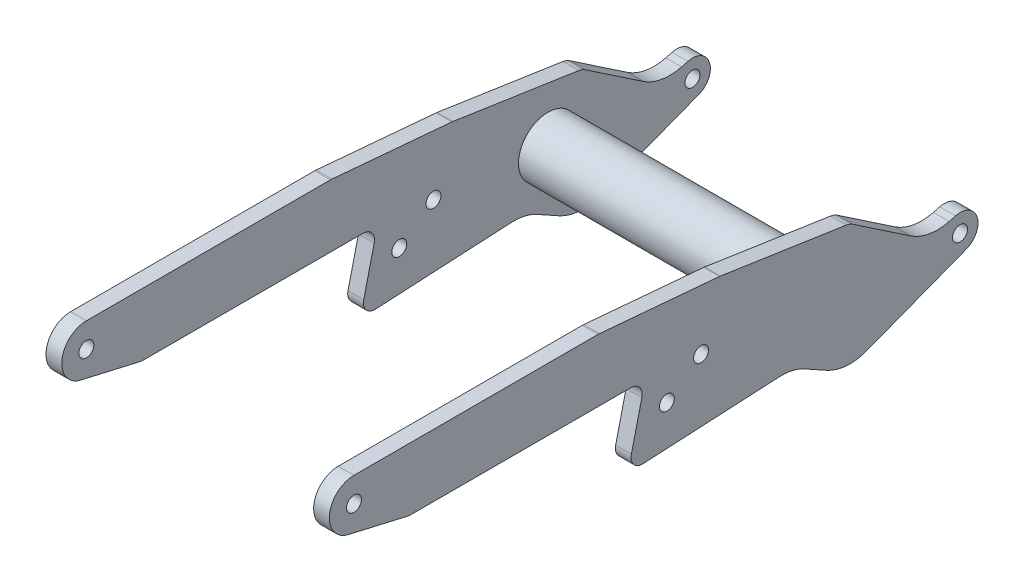
SolidWorks part; units mm, degrees
ref_plane "Front Plane" through (0, 0, 0) normal (0, 0, 1) x (1, 0, 0)
ref_plane "Top Plane" through (0, 0, 0) normal (0, 1, 0) x (1, 0, 0)
ref_plane "Right Plane" through (0, 0, 0) normal (1, 0, 0) x (0, 0, -1)
sketch "Sketch1" plane through (0, 0, 0) normal (1, 0, 0) x (0, 0, -1)
  line L0 (0, 15.625) -> (155.5, 15.625)
  line L1 (0, 0) -> (0, 24.103) construction
  line L2 (0, 0) -> (385.2736, 0) construction
  line L3 (155.5, 15.625) -> (232.5, 8.8884)
  line L4 (232.5, 8.8884) -> (315, -3.4413)
  line L5 (315, -3.4413) -> (353.7804, -29.5991)
  line L6 (378.0985, -33.7644) -> (382.1339, -32.7162)
  line L7 (-3.5149, -15.2245) -> (35, -24.1164)
  line L8 (35, -24.1164) -> (175.8144, -24.1164)
  line L9 (182.866, -33.0507) -> (176.2129, -60.9055)
  line L10 (183.6448, -69.8298) -> (270.1595, -65.2859)
  line L11 (286.2743, -69.0044) -> (300.5448, -76.9126)
  line L12 (325.8403, -78.6785) -> (389.0866, -54.3924)
  circle A0 centre (0, 0) radius 4.75
  circle A1 centre (198.75, -43.75) radius 4.75
  circle A2 centre (220.5, -28) radius 4.75
  circle A3 centre (385, -43.75) radius 4.75
  arc A4 (0, 15.625) -> (-3.5149, -15.2245) centre (0, 0) ccw
  arc A5 (382.1339, -32.7162) -> (389.0866, -54.3924) centre (385, -43.75) cw
  arc A6 (353.7804, -29.5991) -> (378.0985, -33.7644) centre (370.5562, -4.7279) ccw
  arc A7 (325.8403, -78.6785) -> (300.5448, -76.9126) centre (315.0861, -50.6723) cw
  arc A8 (286.2743, -69.0044) -> (270.1595, -65.2859) centre (271.7329, -95.2446) ccw
  arc A9 (183.6448, -69.8298) -> (176.2129, -60.9055) centre (183.2645, -62.5898) cw
  arc A10 (182.866, -33.0507) -> (175.8144, -24.1164) centre (175.8144, -31.3664) ccw
  point P26 (365, -37.1668)
  point P31 (278.75, -64.8347)
  point P36 (185, -24.1164)
  dimension "D1" = 9.5
  dimension "D8" = 15.625
  dimension "D9" = 154.5
  dimension "D15" = 11.4
  dimension "D17" = 35
  dimension "D24" = 30
  dimension "D25" = 7.25
  dimension "D2" = 198.75
  dimension "D3" = 43.75
  dimension "D4" = 220.5
  dimension "D5" = 28
  dimension "D6" = 385
  dimension "D7" = 43.75
  dimension "D10" = 155.5
  dimension "D11" = 232.5
  dimension "D12" = 315
  dimension "D13" = 175
  dimension "D14" = 176.5
  dimension "D16" = 50
  dimension "D18" = 167
  dimension "D19" = 150
  dimension "D20" = 73.56
  dimension "D21" = 148
  dimension "D22" = 130
  dimension "D23" = 80
extrude "Boss-Extrude1" add sketch "Sketch1" along normal mid plane 180
fillet "Fillet1" radius 10 4 edges at (0, -24.1164, -35) (0, -3.4413, -315) (0, 8.8884, -232.5) (0, 15.625, -155.5)
ref_plane "Plane2" through (0, 15.625, 0) normal (0, 1, 0) x (1, 0, 0)
sketch "Sketch4" plane through (0, 15.625, 0) normal (0, 1, 0) x (1, 0, 0)
  line L0 (-90, -15.625) -> (90, -15.625) construction
  line L1 (-80, -15.625) -> (80, -15.625)
  line L2 (-80, -15.625) -> (-80, 396.4)
  line L3 (-80, 396.4) -> (80, 396.4)
  line L4 (80, -15.625) -> (80, 396.4)
  line L5 (90, 396.4) -> (-90, 396.4) construction
  line L6 (-90, 155.0634) -> (-90, 0) construction
  line L7 (90, 312.7621) -> (90, 232.8022) construction
  dimension "D1" = 10
  dimension "D2" = 10
extrude "Cut-Extrude2" cut sketch "Sketch4" against normal through all
ref_plane "Plane3" through (0, 0, 0) normal (1, 0, 0) x (0, 0, -1)
sketch "Sketch5" plane through (0, 0, 0) normal (1, 0, 0) x (0, 0, -1)
  circle A0 centre (293.25, -35) radius 18.75
  dimension "D1" = 37.5
  dimension "D2" = 293.25
  dimension "D3" = 35
extrude "Boss-Extrude3" add sketch "Sketch5" along normal mid plane 180
